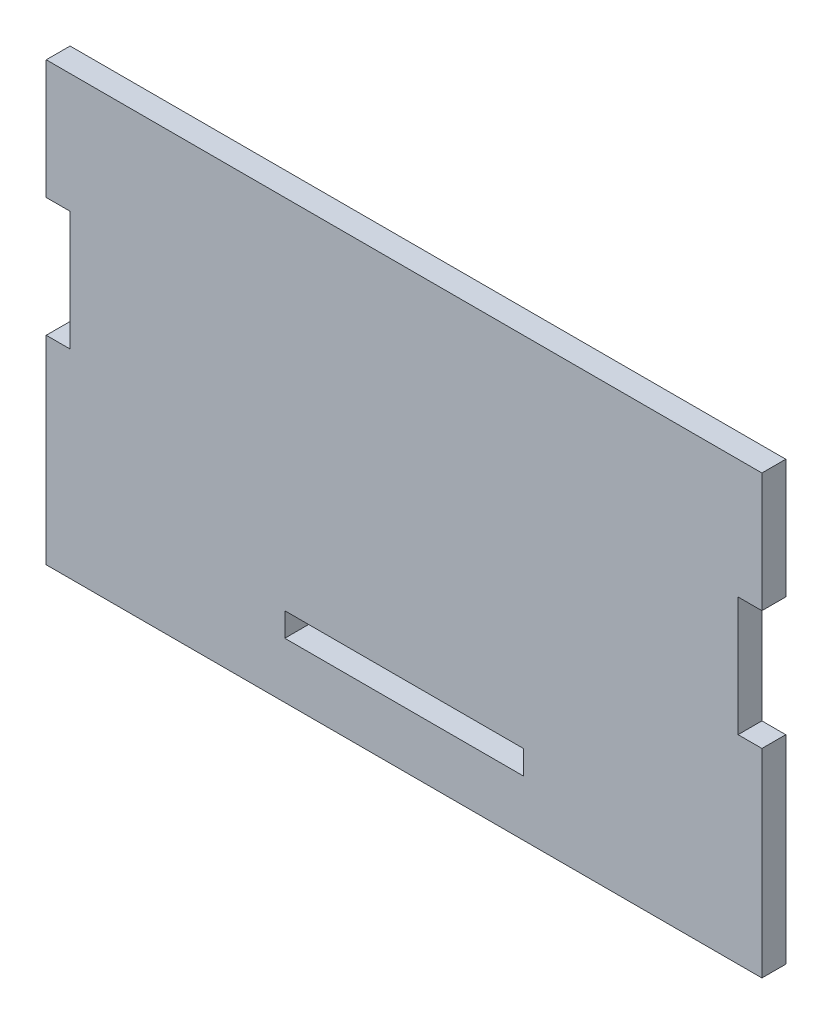
SolidWorks part; units mm, degrees
ref_plane "Front Plane" through (0, 0, 0) normal (0, 0, 1) x (1, 0, 0)
ref_plane "Top Plane" through (0, 0, 0) normal (0, 1, 0) x (1, 0, 0)
ref_plane "Right Plane" through (0, 0, 0) normal (1, 0, 0) x (0, 0, -1)
sketch "Sketch1" plane through (0, 0, 0) normal (0, 0, 1) x (1, 0, 0)
  line L0 (-45, 12.5) -> (-42, 12.5)
  line L1 (-45, -27.5) -> (45, -27.5)
  line L2 (-45, -27.5) -> (-45, 27.5)
  line L3 (-45, 27.5) -> (45, 27.5)
  line L4 (45, -27.5) -> (45, 27.5)
  line L5 (-45, -27.5) -> (45, 27.5) construction
  line L6 (-45, 27.5) -> (45, -27.5) construction
  line L7 (-42, 12.5) -> (-42, -2.5)
  line L8 (-42, -2.5) -> (-45, -2.5)
  line L9 (45, -2.5) -> (42, -2.5)
  line L10 (42, -2.5) -> (42, 12.5)
  line L11 (42, 12.5) -> (45, 12.5)
  line L13 (-15, -20.5) -> (15, -20.5)
  line L14 (-15, -20.5) -> (-15, -17.5)
  line L15 (-15, -17.5) -> (15, -17.5)
  line L16 (15, -20.5) -> (15, -17.5)
  line L17 (-15, -20.5) -> (15, -17.5) construction
  line L18 (-15, -17.5) -> (15, -20.5) construction
  point P0 (0, 0)
  point P12 (0, -19)
  dimension "D1" = 90
  dimension "D2" = 55
  dimension "D3" = 15
  dimension "D4" = 25
  dimension "D5" = 15
  dimension "D6" = 3
  dimension "D7" = 3
  dimension "D8" = 30
  dimension "D9" = 3
  dimension "D10" = 0
  dimension "D11" = 7
extrude "Boss-Extrude1" add sketch "Sketch1" along normal blind 3 contours L3 L2 L0 L7 L8 L1 L4 region at (0, 0.2642, 0)
